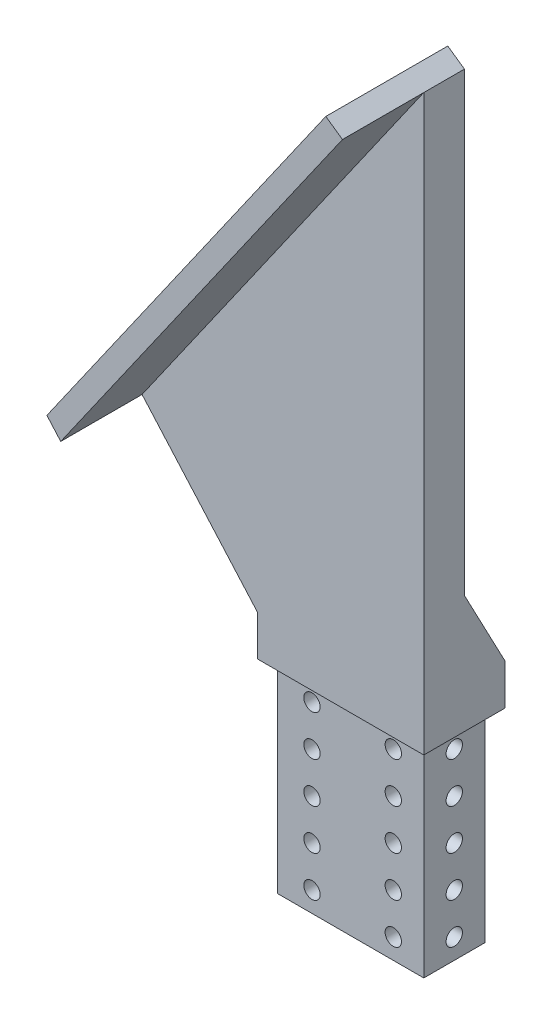
SolidWorks part; units mm, degrees
material "6061-T6 (SS)"
ref_plane "Front Plane" through (0, 0, 0) normal (0, 0, 1) x (1, 0, 0)
ref_plane "Top Plane" through (0, 0, 0) normal (0, 1, 0) x (1, 0, 0)
ref_plane "Right Plane" through (0, 0, 0) normal (1, 0, 0) x (0, 0, -1)
sketch "Sketch1" plane through (0, 0, 0) normal (0, 0, 1) x (1, 0, 0)
  line L0 (0, 0) -> (0, 76.2)
  line L1 (0, 76.2) -> (-101, 76.2)
  line L2 (-101, 76.2) -> (-101, 254)
  line L3 (-101, 254) -> (153, 254)
  line L4 (153, 254) -> (153, 76.2)
  line L5 (153, 76.2) -> (52, 76.2)
  line L6 (52, 76.2) -> (52, 0)
  line L7 (52, 0) -> (0, 0)
  point P3 (26, 254)
  dimension "D1" = 254
  dimension "D2" = 177.8
  dimension "D3" = 76.2
extrude "Boss-Extrude1" add sketch "Sketch1" along normal blind 25.4
sketch "Sketch2" plane through (0, 0, 25.4) normal (0, 0, 1) x (1, 0, 0)
  line L0 (52, 0) -> (52, 76.2) construction
  line L1 (0, 0) -> (52, 0)
  line L2 (0, 0) -> (0, 63.5)
  line L3 (0, 63.5) -> (52, 63.5)
  line L4 (52, 0) -> (52, 63.5)
  dimension "D1" = 63.5
sketch "Sketch3" plane through (0, 0, 0) normal (-1, 0, 0) x (0, 0, 1)
  line L0 (25.4, 0) -> (25.4, 63.5) construction
  line L1 (25.4, 63.5) -> (0, 63.5)
  line L2 (25.4, 63.5) -> (25.4, 0)
  line L3 (25.4, 0) -> (0, 0)
  line L4 (0, 63.5) -> (0, 0)
sketch "Sketch4" plane through (0, 0, 0) normal (0, 0, -1) x (-1, 0, 0)
  line L1 (0, 63.5) -> (-52, 63.5)
  line L2 (0, 63.5) -> (0, 0)
  line L3 (0, 0) -> (-52, 0)
  line L4 (-52, 63.5) -> (-52, 0)
sketch "Sketch5" plane through (52, 0, 0) normal (1, 0, 0) x (0, 0, -1)
  line L1 (0, 63.5) -> (-25.4, 63.5)
  line L2 (0, 63.5) -> (0, 0)
  line L3 (0, 0) -> (-25.4, 0)
  line L4 (-25.4, 63.5) -> (-25.4, 0)
extrude "Cut-Extrude1" cut sketch "Sketch2" against normal blind 3.175
extrude "Cut-Extrude2" cut sketch "Sketch3" against normal blind 3.175
extrude "Cut-Extrude3" cut sketch "Sketch4" against normal blind 3.175
extrude "Cut-Extrude4" cut sketch "Sketch5" against normal blind 3.175
sketch "Sketch6" plane through (0, 0, 3.175) normal (0, 0, -1) x (-1, 0, 0)
  line L0 (-48.825, 63.5) -> (-48.825, 0) construction
  line L1 (-3.175, 63.5) -> (-48.825, 63.5) construction
  line L2 (-48.825, 0) -> (-3.175, 0) construction
  circle A0 centre (-39.3, 57.15) radius 2.5527
  circle A1 centre (-13.9, 57.15) radius 2.5527
  circle A2 centre (-39.3, 44.45) radius 2.5527
  circle A3 centre (-13.9, 44.45) radius 2.5527
  circle A4 centre (-39.3, 31.75) radius 2.5527
  circle A5 centre (-13.9, 31.75) radius 2.5527
  circle A6 centre (-39.3, 19.05) radius 2.5527
  circle A7 centre (-13.9, 19.05) radius 2.5527
  circle A8 centre (-39.3, 6.35) radius 2.5527
  circle A9 centre (-13.9, 6.35) radius 2.5527
  dimension "D1" = 25.4
  dimension "D2" = 9.525
  dimension "D3" = 5.1054
  dimension "D4" = 5.1054
  dimension "D5" = 6.35
  dimension "D7" = 12.7
  dimension "D8" = 6.35
  dimension "D6" = 5
sketch "Sketch7" plane through (48.825, 0, 0) normal (1, 0, 0) x (0, 0, -1)
  line L0 (0, 63.5) -> (-25.4, 63.5) construction
  line L1 (-22.225, 0) -> (-22.225, 63.5) construction
  circle A0 centre (-12.7, 57.15) radius 2.5527
  circle A1 centre (-12.7, 44.45) radius 2.5527
  circle A2 centre (-12.7, 31.75) radius 2.5527
  circle A3 centre (-12.7, 19.05) radius 2.5527
  circle A4 centre (-12.7, 6.35) radius 2.5527
  dimension "D1" = 5.1054
  dimension "D2" = 6.35
  dimension "D3" = 9.525
  dimension "D5" = 12.7
  dimension "D4" = 5
extrude "Cut-Extrude5" cut sketch "Sketch6" against normal through all
extrude "Cut-Extrude6" cut sketch "Sketch7" against normal through all
sketch "Sketch8" plane through (0, 0, 25.4) normal (0, 0, 1) x (1, 0, 0)
  line L1 (52, 76.2) -> (153, 76.2)
  line L2 (52, 76.2) -> (52, 254)
  line L3 (52, 254) -> (153, 254)
  line L4 (153, 76.2) -> (153, 254)
extrude "Cut-Extrude7" cut sketch "Sketch8" against normal through all
sketch "Sketch9" plane through (0, 0, 25.4) normal (0, 0, 1) x (1, 0, 0)
  line L0 (52, 254) -> (52, 242.697)
  line L1 (52, 63.5) -> (52, 254) construction
  line L2 (52, 242.697) -> (35.8576, 254)
  line L3 (52, 254) -> (-101, 254) construction
  line L4 (35.8576, 254) -> (52, 254)
  dimension "D1" = 35
  dimension "D2" = 11.303
extrude "Cut-Extrude8" cut sketch "Sketch9" against normal through all and the other way through all
sketch "Sketch10" plane through (0, 0, 25.4) normal (0, 0, 1) x (1, 0, 0)
  line L0 (35.8576, 254) -> (-101, 58.547)
  line L1 (-101, 58.547) -> (-101, 254)
  line L2 (-101, 254) -> (35.8576, 254)
  dimension "D1" = 55
extrude "Cut-Extrude9" cut sketch "Sketch10" against normal through all
sketch "Sketch11" plane through (0, 0, 25.4) normal (0, 0, 1) x (1, 0, 0)
  line L0 (35.8576, 254) -> (46.7977, 246.3397)
  line L1 (52, 242.697) -> (35.8576, 254) construction
  line L2 (46.7977, 246.3397) -> (-82.8298, 61.2124)
  line L3 (-82.8298, 61.2124) -> (-93.7699, 68.8727)
  line L4 (-93.7699, 68.8727) -> (35.8576, 254)
  dimension "D1" = 13.3553
  dimension "D2" = 13.3553
  dimension "D3" = 225.9987
extrude "Cut-Extrude10" cut sketch "Sketch11" against normal through all
sketch "Sketch14" plane through (0, 0, 25.4) normal (0, 0, 1) x (1, 0, 0)
  line L1 (46.7977, 246.3397) -> (52, 242.697)
  line L2 (52, 242.697) -> (-80.3885, 53.6266)
  line L3 (-80.3885, 53.6266) -> (-85.5908, 57.2693)
  line L4 (-85.5908, 57.2693) -> (46.7977, 246.3397)
extrude "Boss-Extrude2" add sketch "Sketch14" along normal blind 25.4
sketch "Sketch15" plane through (0, 0, 50.8) normal (0, 0, 1) x (1, 0, 0)
  line L0 (-64.5825, 76.2) -> (-72.3354, 76.2)
  line L1 (-72.3354, 76.2) -> (-85.5908, 57.2693)
  line L2 (-85.5908, 57.2693) -> (-80.3885, 53.6266)
  line L3 (-80.3885, 53.6266) -> (-64.5825, 76.2)
extrude "Cut-Extrude11" cut sketch "Sketch15" against normal through all
sketch "Sketch16" plane through (0, 0, 0) normal (0, 0, -1) x (-1, 0, 0)
  line L0 (0, 76.2) -> (40.323, 121.9184)
  line L1 (72.3354, 76.2) -> (-46.7977, 246.3397) construction
  line L2 (40.323, 121.9184) -> (72.3354, 76.2)
  line L3 (72.3354, 76.2) -> (0, 76.2)
  dimension "D1" = 60.96
extrude "Cut-Extrude12" cut sketch "Sketch16" against normal through all
sketch "Sketch17" plane through (52, 0, 0) normal (1, 0, 0) x (0, 0, -1)
  line L0 (-12.7, 246.3397) -> (-12.7, 100.2897)
  line L1 (0, 246.3397) -> (-50.8, 246.3397) construction
  line L2 (-12.7, 100.2897) -> (0, 76.2)
  line L3 (0, 63.5) -> (0, 242.697) construction
  line L4 (0, 76.2) -> (0, 246.3397)
  line L5 (0, 246.3397) -> (-12.7, 246.3397)
  dimension "D1" = 12.7
  dimension "D2" = 146.05
  dimension "D3" = 12.7
extrude "Cut-Extrude13" cut sketch "Sketch17" against normal through all
